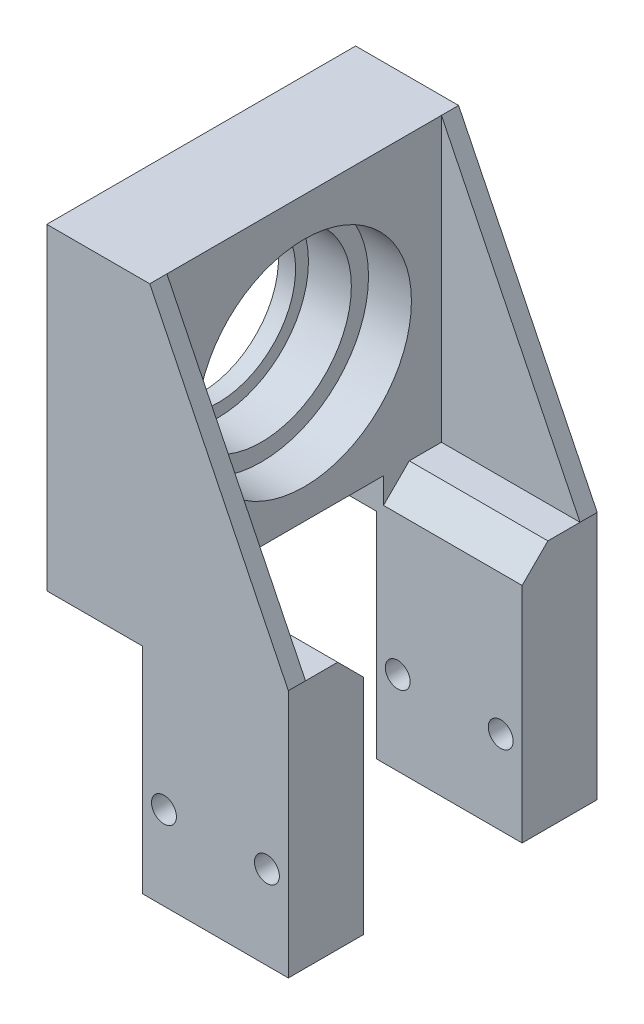
SolidWorks part; units mm, degrees
material "6061 Alloy"
ref_plane "Front Plane" through (0, 0, 0) normal (0, 0, 1) x (1, 0, 0)
ref_plane "Top Plane" through (0, 0, 0) normal (0, 1, 0) x (1, 0, 0)
ref_plane "Right Plane" through (0, 0, 0) normal (1, 0, 0) x (0, 0, -1)
sketch "Sketch1" plane through (0, 0, 0) normal (0, 0, 1) x (1, 0, 0)
  line L0 (0, 0) -> (17, 0)
  line L1 (17, 0) -> (17, 29)
  line L2 (17, 29) -> (0.8434, 29)
  line L3 (0.8434, 29) -> (0.8434, 62)
  line L4 (0.8434, 62) -> (-11.1566, 62)
  line L5 (-11.1566, 62) -> (-11.1566, 25)
  line L6 (-11.1566, 25) -> (0, 25)
  line L7 (0, 25) -> (0, 0)
  dimension "D1" = 17
  dimension "D2" = 62
  dimension "D3" = 25
  dimension "D4" = 12
  dimension "D5" = 4
extrude "Boss-Extrude1" add sketch "Sketch1" along normal blind 36
sketch "Sketch2" plane through (0.8434, 0, 0) normal (1, 0, 0) x (0, 0, -1)
  line L0 (-18, 62) -> (-18, 12.1467) construction
  line L1 (-36, 62) -> (0, 62) construction
  circle A0 centre (-18, 45) radius 10.5
  dimension "D1" = 21
  dimension "D2" = 17
extrude "Cut-Extrude1" cut sketch "Sketch2" against normal through all
sketch "Sketch3" plane through (17, 0, 0) normal (1, 0, 0) x (0, 0, -1)
  line L0 (-36, 0) -> (0, 0) construction
  line L1 (-27.25, 0) -> (-8.75, 0)
  line L2 (-27.25, 0) -> (-27.25, 29)
  line L3 (-27.25, 29) -> (-8.75, 29)
  line L4 (-8.75, 0) -> (-8.75, 29)
  line L5 (-36, 29) -> (0, 29) construction
  line L6 (-18, 0) -> (-18, 45) construction
  dimension "D1" = 18.5
extrude "Cut-Extrude2" cut sketch "Sketch3" against normal through all
sketch "Sketch4" plane through (0, 0, 36) normal (0, 0, 1) x (1, 0, 0)
  line L0 (0.8434, 62) -> (17, 29)
rib "Rib1" sketch "Sketch4" sketch "Sketch4" thickness 2 extrusion direction parallel to sketch draft on no parameters "D1"=2
sketch "Sketch5" plane through (0, 0, 0) normal (0, 0, -1) x (-1, 0, 0)
  line L0 (-0.8434, 62) -> (-17, 29)
rib "Rib2" sketch "Sketch5" sketch "Sketch5" thickness 2 extrusion direction parallel to sketch draft on no parameters "D1"=2
chamfer "Chamfer1" distance 3 angle 45 2 edges at (8.9217, 29, 27.25) (8.9217, 29, 8.75)
sketch "Sketch6" plane through (-11.1566, 0, 0) normal (-1, 0, 0) x (0, 0, 1)
  circle A0 centre (18, 45) radius 10.5 construction
  circle A1 centre (18, 45) radius 10.5
  circle A2 centre (18, 45) radius 9
  dimension "D1" = 1.5
extrude "Boss-Extrude2" add sketch "Sketch6" against normal blind 2
sketch "Sketch9" plane through (0, 0, 36) normal (0, 0, 1) x (1, 0, 0)
  line L0 (2.5, 9.75) -> (14.5, 9.75) construction
  line L2 (0, 0) -> (17, 0) construction
  line L3 (8.5, 0) -> (8.5, 9.75) construction
  line L4 (-11.1566, 25) -> (0, 25) construction
  point P0 (2.5, 9.75)
  point P2 (14.5, 9.75)
  dimension "D1" = 12
  dimension "D2" = 15.25
hole_wizard "M2.5 Clearance Hole1" positions "Sketch9" profile "Sketch8" hole size "M2.5" standard "DIN" end condition through all
sketch "Sketch8" plane through (2.5, 9.75, 36) normal (1, 0, 0) x (0, -1, 0)
  line L0 (0, 0) -> (0, 36)
  line L1 (0, 36) -> (1.45, 36)
  line L2 (1.45, 36) -> (1.45, 0)
  line L5 (1.45, 0) -> (0, 0)
  line L11 (0, -6.35) -> (0, 107.95) construction
  dimension "Thru Hole Dia." = 2.9
  dimension "Thru Hole Depth" = 36
sketch "Sketch10" plane through (-11.1566, 0, 0) normal (-1, 0, 0) x (0, 0, 1)
  circle A0 centre (18, 45) radius 11
  circle A1 centre (18, 45) radius 15
  dimension "D1" = 22
  dimension "D2" = 30
extrude "Cut-Extrude4" cut sketch "Sketch10" against normal blind 0.6
sketch "Sketch11" plane through (0.8434, 0, 0) normal (1, 0, 0) x (0, 0, -1)
  circle A0 centre (-18, 45) radius 12.5
  dimension "D1" = 25
extrude "Cut-Extrude5" cut sketch "Sketch11" against normal blind 5
